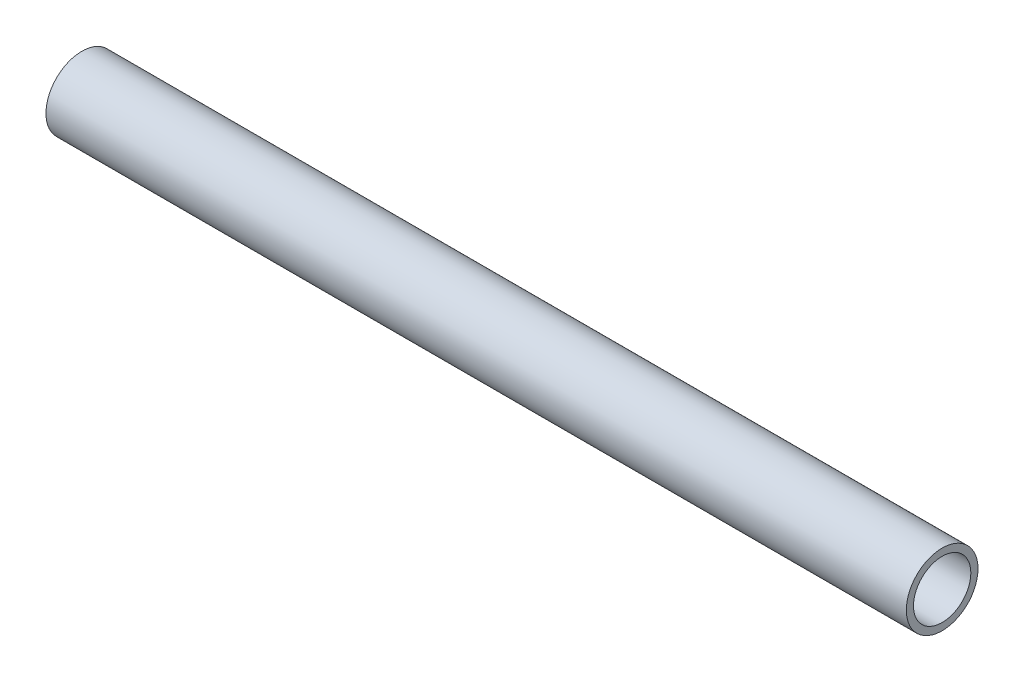
SolidWorks part; units mm, degrees
ref_plane "Front Plane" through (0, 0, 0) normal (0, 0, 1) x (1, 0, 0)
ref_plane "Top Plane" through (0, 0, 0) normal (0, 1, 0) x (1, 0, 0)
ref_plane "Right Plane" through (0, 0, 0) normal (1, 0, 0) x (0, 0, -1)
sketch "Sketch1" plane through (0, 0, 0) normal (0, 0, 1) x (1, 0, 0)
  line L0 (0, 0) -> (120, 0)
  dimension "D1" = 120
sweep "Sweep-Thin1" add path "Sketch1" circular profile diameter 10 parameters "D1"=1, "D3"=10
